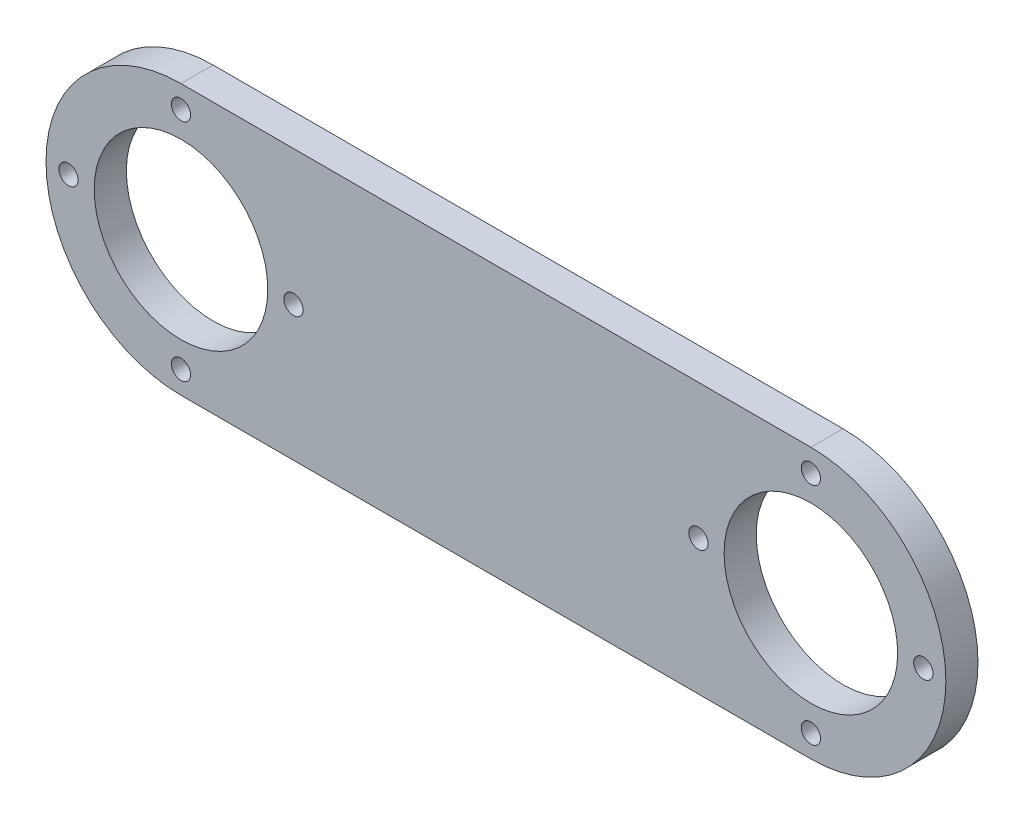
SolidWorks part; units mm, degrees
material "Thornel Mat VMA"
ref_plane "Front Plane" through (0, 0, 0) normal (0, 0, 1) x (1, 0, 0)
ref_plane "Top Plane" through (0, 0, 0) normal (0, 1, 0) x (1, 0, 0)
ref_plane "Right Plane" through (0, 0, 0) normal (1, 0, 0) x (0, 0, -1)
sketch "Sketch1" plane through (0, 0, 0) normal (0, 0, 1) x (1, 0, 0)
  line L0 (49, 26) -> (-49, 26) construction
  line L1 (-49, -16) -> (49, -16) construction
  line L2 (49, 26) -> (-49, 26)
  line L3 (-49, -16) -> (49, -16)
  circle A0 centre (49, 5) radius 21 construction
  circle A2 centre (-49, 5) radius 13 construction
  circle A3 centre (-66.5, 5) radius 1.5 construction
  circle A4 centre (-49, 22.5) radius 1.5 construction
  circle A5 centre (-31.5, 5) radius 1.5 construction
  circle A6 centre (-49, -12.5) radius 1.5 construction
  circle A7 centre (49, 5) radius 13 construction
  circle A8 centre (31.5, 5) radius 1.5 construction
  circle A9 centre (49, 22.5) radius 1.5 construction
  circle A10 centre (66.5, 5) radius 1.5 construction
  circle A11 centre (49, -12.5) radius 1.5 construction
  arc A12 (49, -16) -> (49, 26) centre (49, 5) ccw
  circle A14 centre (-49, 5) radius 13
  circle A15 centre (-66.5, 5) radius 1.5
  circle A16 centre (-49, 22.5) radius 1.5
  circle A17 centre (-31.5, 5) radius 1.5
  circle A18 centre (-49, -12.5) radius 1.5
  circle A19 centre (49, 5) radius 13
  circle A20 centre (31.5, 5) radius 1.5
  circle A21 centre (49, 22.5) radius 1.5
  circle A22 centre (66.5, 5) radius 1.5
  circle A23 centre (49, -12.5) radius 1.5
  arc A24 (-49, 26) -> (-49, -16) centre (-49, 5) ccw
extrude "Boss-Extrude1" add sketch "Sketch1" along normal blind 5
sketch "Sketch2" plane through (0, 0, 0) normal (0, 0, -1) x (-1, 0, 0)
  circle A0 centre (-49, 5) radius 13.5
  circle A1 centre (49, 5) radius 13.5
  dimension "D1" = 27
extrude "Cut-Extrude1" cut sketch "Sketch2" against normal blind 10
